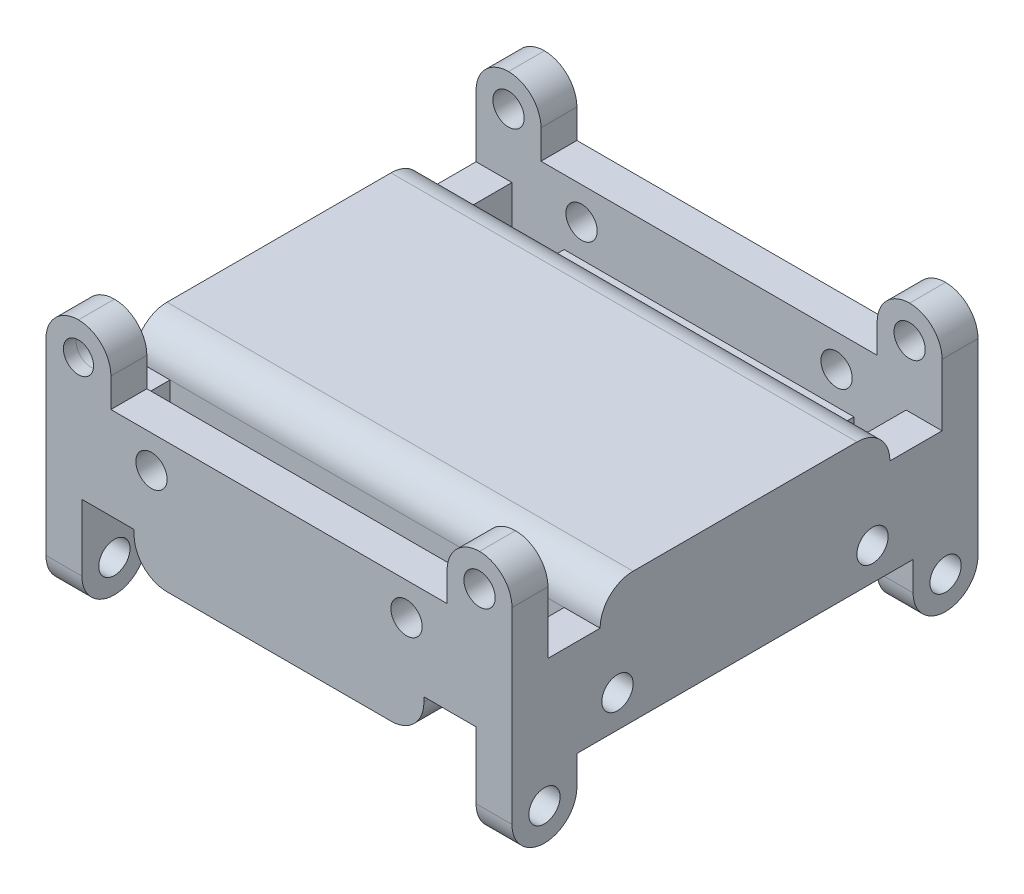
SolidWorks part; units mm, degrees
ref_plane "Plano frontal" through (0, 0, 0) normal (0, 0, 1) x (1, 0, 0)
ref_plane "Plano superior" through (0, 0, 0) normal (0, 1, 0) x (1, 0, 0)
ref_plane "Plano direito" through (0, 0, 0) normal (1, 0, 0) x (0, 0, -1)
sketch "Esboço1" plane through (0, 0, 0) normal (0, 0, 1) x (1, 0, 0)
  line L0 (0, 0) -> (5.6, 0)
  line L1 (0, 0) -> (0, -11.45)
  line L2 (0, -11.45) -> (40.2, -11.45)
  line L3 (40.2, -11.45) -> (40.2, 0)
  line L4 (40.2, 0) -> (34.6, 0)
  line L5 (5.6, 0) -> (5.6, -5.85)
  line L6 (5.6, -5.85) -> (34.6, -5.85)
  line L7 (34.6, -5.85) -> (34.6, 0)
  circle A0 centre (2.8, -3.35) radius 1.35
  circle A1 centre (37.4, -3.35) radius 1.35
  circle A3 centre (31.1, -8.65) radius 1.35
  circle A4 centre (9.1, -8.65) radius 1.35
  dimension "D6" = 2.7
  dimension "D7" = 3.35
  dimension "D8" = 2.7
  dimension "D9" = 2.8
  dimension "D10" = 2.8
  dimension "D11" = 2.7
  dimension "D12" = 2.7
  dimension "D13" = 3.5
  dimension "D14" = 3.5
  dimension "D15" = 2.8
  dimension "D16" = 2.8
  dimension "D17" = 3.35
  dimension "D1" = 5.6
  dimension "D2" = 11.45
  dimension "D3" = 40.2
  dimension "D4" = 5.6
  dimension "D5" = 5.85
extrude "Ressalto-extrusão1" add sketch "Esboço1" along normal blind 2
sketch "Esboço3" plane through (0, -11.45, 0) normal (0, -1, 0) x (1, 0, 0)
  line L1 (0, 0) -> (40.2, 0)
  line L2 (0, 0) -> (0, 2)
  line L3 (0, 2) -> (40.2, 2)
  line L4 (40.2, 0) -> (40.2, 2)
extrude "Ressalto-extrusão2" add sketch "Esboço3" along normal blind 10.08
sketch "Esboço4" plane through (0, 0, 0) normal (0, 0, -1) x (-1, 0, 0)
  line L0 (0, 0) -> (0, -21.53) construction
  line L1 (-40.2, -21.53) -> (-37.1, -21.53)
  line L2 (-40.2, -21.53) -> (-40.2, -8.69)
  line L3 (-40.2, -8.69) -> (-37.1, -8.69)
  line L4 (-37.1, -21.53) -> (-37.1, -8.69)
  line L5 (0, -8.69) -> (-3.1, -8.69)
  line L6 (0, -8.69) -> (0, -21.53)
  line L7 (0, -21.53) -> (-3.1, -21.53)
  line L8 (-3.1, -8.69) -> (-3.1, -21.53)
  line L9 (0, -21.53) -> (-40.2, -21.53) construction
  dimension "D1" = 12.84
  dimension "D2" = 3.1
  dimension "D3" = 3.1
  dimension "D4" = 12.84
extrude "Ressalto-extrusão3" add sketch "Esboço4" along normal blind 34
sketch "Esboço5" plane through (37.1, 0, 0) normal (-1, 0, 0) x (0, 0, 1)
  line L0 (0, -21.53) -> (0, -8.69) construction
  line L2 (-34, -21.53) -> (0, -21.53) construction
  line L4 (-34, -21.53) -> (-34, -8.69) construction
  circle A0 centre (-6, -14.25) radius 1.35
  circle A2 centre (-28, -14.25) radius 1.35
  dimension "D1" = 2.7
  dimension "D2" = 2.7
  dimension "D3" = 6
  dimension "D4" = 7.28
  dimension "D5" = 7.28
  dimension "D6" = 6
extrude "Corte-extrusão1" cut sketch "Esboço5" against normal through all both and the other way through all
sketch "Esboço7" plane through (0, 0, 0) normal (0, 0, -1) x (-1, 0, 0)
  line L0 (0, 0) -> (0, -8.69) construction
  line L1 (-37.1, -21.53) -> (0, -21.53)
  line L2 (-37.1, -21.53) -> (-37.1, -18.29)
  line L3 (-37.1, -18.29) -> (0, -18.29)
  line L4 (0, -21.53) -> (0, -18.29)
  dimension "D1" = 3.24
extrude "Corte-extrusão2" cut sketch "Esboço7" against normal blind 2
sketch "Esboço12" plane through (0, 0, -34) normal (0, 0, -1) x (-1, 0, 0)
  line L0 (-5.6, 0) -> (0, 0)
  line L1 (-40.2, 0) -> (-34.6, 0)
  line L2 (-40.2, 0) -> (-40.2, -18.29)
  line L3 (-40.2, -18.29) -> (0, -18.29)
  line L4 (0, 0) -> (0, -18.29)
  line L6 (-34.6, 0) -> (-34.6, -5.85)
  line L7 (-34.6, -5.85) -> (-5.6, -5.85)
  line L8 (-5.6, 0) -> (-5.6, -5.85)
  circle A1 centre (-31.1, -8.65) radius 1.35
  circle A2 centre (-9.1, -8.65) radius 1.35
  circle A3 centre (-2.8, -3.35) radius 1.35
  circle A4 centre (-37.4, -3.35) radius 1.35
extrude "Ressalto-extrusão5" add sketch "Esboço12" along normal blind 2
sketch "Esboço18" plane through (0, 0, 0) normal (0, 0, 1) x (1, 0, 0)
  line L0 (3.1, -18.29) -> (3.1, -21.53) construction
  line L1 (0, -18.29) -> (3.1, -18.29)
  line L2 (0, -18.29) -> (0, -21.53)
  line L3 (0, -21.53) -> (3.1, -21.53)
  line L4 (3.1, -18.29) -> (3.1, -21.53)
extrude "Ressalto-extrusão6" add sketch "Esboço18" along normal blind 2
sketch "Esboço19" plane through (0, 0, -34) normal (0, 0, -1) x (-1, 0, 0)
  line L0 (0, -21.53) -> (0, -18.29) construction
  line L1 (-3.1, -21.53) -> (0, -21.53)
  line L2 (-3.1, -21.53) -> (-3.1, -18.29)
  line L3 (-3.1, -18.29) -> (0, -18.29)
  line L4 (0, -21.53) -> (0, -18.29)
  line L6 (-40.2, -21.53) -> (-37.1, -21.53)
  line L7 (-40.2, -21.53) -> (-40.2, -18.29)
  line L8 (-40.2, -18.29) -> (-37.1, -18.29)
  line L9 (-37.1, -21.53) -> (-37.1, -18.29)
extrude "Ressalto-extrusão7" add sketch "Esboço19" along normal blind 2
sketch "Esboço21" plane through (0, 0, 2) normal (0, 0, 1) x (1, 0, 0)
  line L0 (37.1, -21.53) -> (40.2, -21.53)
  line L1 (0, 0) -> (5.6, 0)
  line L2 (0, 0) -> (0, -21.53)
  line L3 (0, -21.53) -> (3.1, -21.53)
  line L4 (40.2, 0) -> (40.2, -21.53)
  line L6 (5.6, 0) -> (5.6, -5.85)
  line L7 (5.6, -5.85) -> (34.6, -5.85)
  line L8 (34.6, 0) -> (34.6, -5.85)
  line L9 (3.1, -18.29) -> (37.1, -18.29)
  line L10 (3.1, -18.29) -> (3.1, -21.53)
  line L12 (37.1, -18.29) -> (37.1, -21.53)
  line L13 (34.6, 0) -> (40.2, 0)
  circle A0 centre (2.8, -3.35) radius 1.3018
  circle A1 centre (9.1, -8.65) radius 1.35
  circle A2 centre (31.1, -8.65) radius 1.35
  circle A3 centre (37.4, -3.35) radius 1.35
extrude "Ressalto-extrusão8" add sketch "Esboço21" along normal blind 1.1
sketch "Esboço22" plane through (0, 0, -36) normal (0, 0, -1) x (-1, 0, 0)
  line L0 (-5.6, 0) -> (0, 0)
  line L1 (-40.2, 0) -> (-34.6, 0)
  line L2 (-40.2, 0) -> (-40.2, -21.53)
  line L3 (-40.2, -21.53) -> (-37.1, -21.53)
  line L4 (0, 0) -> (0, -21.53)
  line L6 (-37.1, -21.53) -> (-37.1, -18.29)
  line L7 (-37.1, -18.29) -> (-3.1, -18.29)
  line L8 (-3.1, -21.53) -> (-3.1, -18.29)
  line L9 (-34.6, -5.85) -> (-5.6, -5.85)
  line L10 (-34.6, -5.85) -> (-34.6, 0)
  line L12 (-5.6, -5.85) -> (-5.6, 0)
  line L13 (-3.1, -21.53) -> (0, -21.53)
  circle A0 centre (-37.4, -3.35) radius 1.35
  circle A1 centre (-31.1, -8.65) radius 1.35
  circle A2 centre (-9.1, -8.65) radius 1.35
  circle A3 centre (-2.8, -3.35) radius 1.35
extrude "Ressalto-extrusão9" add sketch "Esboço22" along normal blind 1.1
sketch "Esboço23" plane through (0, -21.53, 0) normal (0, -1, 0) x (1, 0, 0)
  line L0 (3.1, -37.1) -> (3.1, 3.1) construction
  line L1 (0, 3.1) -> (3.1, 3.1)
  line L2 (0, 3.1) -> (0, -2.5)
  line L3 (0, -2.5) -> (3.1, -2.5)
  line L4 (3.1, 3.1) -> (3.1, -2.5)
  line L5 (40.2, -37.1) -> (40.2, 3.1) construction
  line L6 (0, -37.1) -> (3.1, -37.1)
  line L7 (0, -37.1) -> (0, -31.5)
  line L8 (0, -31.5) -> (3.1, -31.5)
  line L9 (3.1, -37.1) -> (3.1, -31.5)
  line L10 (37.1, -37.1) -> (40.2, -37.1)
  line L11 (37.1, -37.1) -> (37.1, -31.5)
  line L12 (37.1, -31.5) -> (40.2, -31.5)
  line L13 (40.2, -37.1) -> (40.2, -31.5)
  line L15 (37.1, 3.1) -> (40.2, 3.1)
  line L16 (37.1, 3.1) -> (37.1, -2.5)
  line L17 (37.1, -2.5) -> (40.2, -2.5)
  line L18 (40.2, 3.1) -> (40.2, -2.5)
  dimension "D1" = 5.6
  dimension "D2" = 5.6
  dimension "D3" = 5.6
  dimension "D4" = 5.6
extrude "Ressalto-extrusão10" add sketch "Esboço23" along normal blind 5.85
sketch "Esboço24" plane through (0, 0, 0) normal (-1, 0, 0) x (0, 0, 1)
  line L1 (-31.5, -27.38) -> (-31.5, -21.53) construction
  line L2 (3.1, 0) -> (3.1, -27.38) construction
  line L3 (3.1, -27.38) -> (-2.5, -27.38) construction
  line L4 (-31.5, -27.38) -> (-37.1, -27.38) construction
  circle A0 centre (-34.3, -19.55) radius 1.35
  circle A1 centre (0.3, -19.55) radius 1.35
  point P10 (0.3, -27.38)
  dimension "D1" = 2.7
  dimension "D2" = 2.7
  dimension "D3" = 2.8
  dimension "D4" = 2.8
  dimension "D5" = 7.83
  dimension "D6" = 7.83
extrude "Corte-extrusão3" cut sketch "Esboço24" against normal up to surface (40.2 mm away) up to face at (40.2, -14.25, -4.65)
sketch "Esboço25" plane through (0, -18.29, 0) normal (0, -1, 0) x (1, 0, 0)
  line L6 (3.1, -37.1) -> (7.6, -37.1)
  line L7 (3.1, -37.1) -> (3.1, -34)
  line L8 (3.1, -34) -> (7.6, -34)
  line L9 (37.1, -37.1) -> (37.1, -34)
  line L10 (32.6, 3.1) -> (37.1, 3.1)
  line L11 (3.1, 3.1) -> (7.6, 3.1)
  line L16 (3.1, 3.1) -> (3.1, 0)
  line L17 (3.1, 0) -> (7.6, 0)
  line L18 (37.1, 3.1) -> (37.1, 0)
  line L22 (7.6, 3.1) -> (7.6, 0)
  line L25 (37.1, 0) -> (32.6, 0)
  line L26 (32.6, 3.1) -> (32.6, 0)
  line L28 (32.6, -34) -> (37.1, -34)
  line L32 (7.6, -34) -> (7.6, -37.1)
  line L33 (37.1, -37.1) -> (32.6, -37.1)
  line L36 (32.6, -37.1) -> (32.6, -34)
  dimension "D1" = 4.5
  dimension "D2" = 4.5
  dimension "D3" = 4.5
  dimension "D4" = 4.5
sketch "Esboço27" plane through (0, -21.53, 0) normal (0, -1, 0) x (1, 0, 0)
  line L28 (0, -2.5) -> (3.1, -2.5)
  line L29 (0, -2.5) -> (0, -31.5)
  line L30 (0, -31.5) -> (3.1, -31.5)
  line L31 (3.1, -2.5) -> (3.1, -31.5)
  line L32 (40.2, -2.5) -> (37.1, -2.5)
  line L33 (40.2, -2.5) -> (40.2, -31.5)
  line L34 (40.2, -31.5) -> (37.1, -31.5)
  line L35 (37.1, -2.5) -> (37.1, -31.5)
extrude "Corte-extrusão6" cut sketch "Esboço25" against normal blind 4.48
extrude "Corte-extrusão7" cut sketch "Esboço27" against normal blind 4.48
sketch "Esboço28" plane through (0, -18.29, 0) normal (0, -1, 0) x (1, 0, 0)
  line L1 (7.6, 3.1) -> (32.6, 3.1)
  line L2 (7.6, 3.1) -> (7.6, -37.1)
  line L3 (7.6, -37.1) -> (32.6, -37.1)
  line L4 (32.6, 3.1) -> (32.6, -37.1)
extrude "Corte-extrusão8" cut sketch "Esboço28" against normal blind 1.24
sketch "Esboço29" plane through (0, 0, -34) normal (0, 0, 1) x (1, 0, 0)
  line L1 (7.6, -17.05) -> (32.6, -17.05)
  line L2 (7.6, -17.05) -> (7.6, -11.45)
  line L3 (7.6, -11.45) -> (32.6, -11.45)
  line L4 (32.6, -17.05) -> (32.6, -11.45)
  dimension "D1" = 25
  dimension "D2" = 5.6
extrude "Ressalto-extrusão11" add sketch "Esboço29" along normal up to surface (34 mm away) up to face at (32.45, -8.65, 0)
sketch "Esboço31" plane through (0, -8.69, 0) normal (0, 1, 0) x (1, 0, 0)
  line L40 (0, 34) -> (0, 0) construction
  line L49 (0, 29.5) -> (3.1, 29.5)
  line L50 (0, 29.5) -> (0, 4.5)
  line L51 (0, 4.5) -> (3.1, 4.5)
  line L52 (3.1, 29.5) -> (3.1, 4.5)
  line L53 (3.1, 34) -> (3.1, 0) construction
  line L54 (37.1, 34) -> (37.1, 0) construction
  line L55 (37.1, 29.5) -> (40.2, 29.5)
  line L56 (37.1, 29.5) -> (37.1, 4.5)
  line L57 (37.1, 4.5) -> (40.2, 4.5)
  line L58 (40.2, 29.5) -> (40.2, 4.5)
  line L59 (40.2, 34) -> (40.2, 0) construction
  line L60 (0, 34) -> (3.1, 34) construction
  line L62 (40.2, 0) -> (34.6, 0) construction
  line L63 (34.6, 34) -> (40.2, 34) construction
  dimension "D1" = 25
  dimension "D2" = 4.5
  dimension "D3" = 4.5
  dimension "D4" = 4.5
extrude "Ressalto-extrusão12" add sketch "Esboço31" along normal blind 2.84
sketch "Esboço32" plane through (37.1, 0, 0) normal (-1, 0, 0) x (0, 0, 1)
  line L1 (-29.5, -5.85) -> (-4.5, -5.85)
  line L2 (-29.5, -5.85) -> (-29.5, -11.45)
  line L3 (-29.5, -11.45) -> (-4.5, -11.45)
  line L4 (-4.5, -5.85) -> (-4.5, -11.45)
  dimension "D1" = 25
  dimension "D2" = 5.6
extrude "Ressalto-extrusão13" add sketch "Esboço32" along normal up to surface (34 mm away) up to face at (3.1, -15.3325, -17)
fillet "Filete1" radius 2.84 4 edges at (32.6, -17.05, -17) (7.6, -17.05, -17) (20.1, -5.85, -29.5) (20.1, -5.85, -4.5)
sketch "Esboço33" plane through (0, 0, 0) normal (0, 1, 0) x (1, 0, 0)
  line L1 (0, 37.1) -> (5.6, 37.1)
  line L2 (0, 37.1) -> (0, 34)
  line L3 (0, 34) -> (5.6, 34)
  line L4 (5.6, 37.1) -> (5.6, 34)
  line L5 (34.6, 34) -> (40.2, 34)
  line L6 (34.6, 34) -> (34.6, 37.1)
  line L7 (34.6, 37.1) -> (40.2, 37.1)
  line L8 (40.2, 34) -> (40.2, 37.1)
  line L9 (40.2, -3.1) -> (34.6, -3.1)
  line L10 (40.2, -3.1) -> (40.2, 0)
  line L11 (40.2, 0) -> (34.6, 0)
  line L12 (34.6, -3.1) -> (34.6, 0)
  line L13 (5.6, -3.1) -> (0, -3.1)
  line L14 (5.6, -3.1) -> (5.6, 0)
  line L15 (5.6, 0) -> (0, 0)
  line L16 (0, -3.1) -> (0, 0)
extrude "Corte-extrusão9" cut sketch "Esboço33" against normal blind 0.55
sketch "Esboço35" plane through (0, -27.38, 0) normal (0, -1, 0) x (1, 0, 0)
  line L1 (0, -2.5) -> (3.1, -2.5)
  line L2 (0, -2.5) -> (0, 3.1)
  line L3 (0, 3.1) -> (3.1, 3.1)
  line L4 (3.1, -2.5) -> (3.1, 3.1)
  line L5 (37.1, -2.5) -> (40.2, -2.5)
  line L6 (37.1, -2.5) -> (37.1, 3.1)
  line L7 (37.1, 3.1) -> (40.2, 3.1)
  line L8 (40.2, -2.5) -> (40.2, 3.1)
  line L9 (40.2, -37.1) -> (37.1, -37.1)
  line L10 (40.2, -37.1) -> (40.2, -31.5)
  line L11 (40.2, -31.5) -> (37.1, -31.5)
  line L12 (37.1, -37.1) -> (37.1, -31.5)
  line L13 (3.1, -37.1) -> (0, -37.1)
  line L14 (3.1, -37.1) -> (3.1, -31.5)
  line L15 (3.1, -31.5) -> (0, -31.5)
  line L16 (0, -37.1) -> (0, -31.5)
extrude "Corte-extrusão10" cut sketch "Esboço35" against normal blind 5.03
fillet "Filete2" radius 2.8 16 edges at (34.6, -0.55, 1.55) (40.2, -0.55, 1.55) (0, -0.55, 1.55) (5.6, -0.55, 1.55) (40.2, -0.55, -35.55) (34.6, -0.55, -35.55) (5.6, -0.55, -35.55) (0, -0.55, -35.55) (1.55, -22.35, -31.5) (1.55, -22.35, -37.1) (38.65, -22.35, -37.1) (38.65, -22.35, -31.5) (38.65, -22.35, 3.1) (38.65, -22.35, -2.5) (1.55, -22.35, -2.5) (1.55, -22.35, 3.1)
